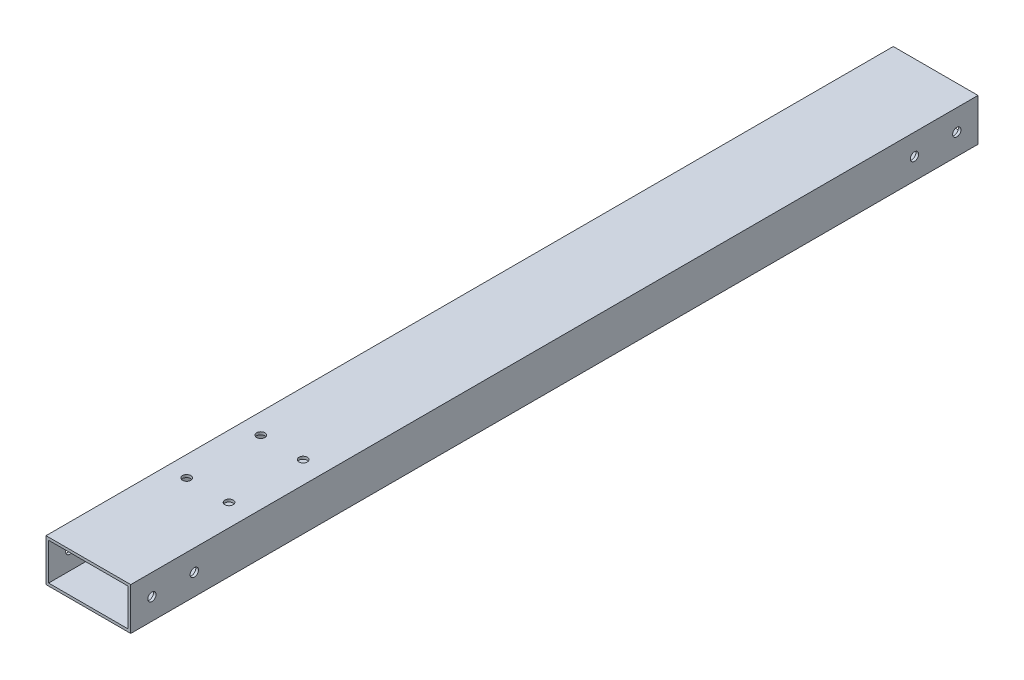
SolidWorks part; units mm, degrees
ref_plane "Front Plane" through (0, 0, 0) normal (0, 0, 1) x (1, 0, 0)
ref_plane "Top Plane" through (0, 0, 0) normal (0, 1, 0) x (1, 0, 0)
ref_plane "Right Plane" through (0, 0, 0) normal (1, 0, 0) x (0, 0, -1)
sketch "Sketch1" plane through (0, 0, 0) normal (0, 0, 1) x (1, 0, 0)
  line L0 (-23.8125, 11.1125) -> (23.8125, 11.1125)
  line L2 (-25.4, 12.7) -> (25.4, 12.7)
  line L3 (-25.4, 12.7) -> (-25.4, -12.7)
  line L4 (-25.4, -12.7) -> (25.4, -12.7)
  line L5 (25.4, 12.7) -> (25.4, -12.7)
  line L10 (23.8125, 11.1125) -> (23.8125, -11.1125)
  line L11 (-23.8125, -11.1125) -> (23.8125, -11.1125)
  line L12 (-23.8125, 11.1125) -> (-23.8125, -11.1125)
  point P12 (0, 12.7)
  point P14 (25.4, 0)
  dimension "Wall Thickness" = 1.5875
  dimension "Outside Width" = 50.8
  dimension "Outside Height" = 25.4
  dimension "Inside Height" = 22.225
  dimension "Inside Width" = 47.625
sketch "Sketch2" plane through (0, 0, 0) normal (1, 0, 0) x (0, 0, -1)
  line L0 (254, 0) -> (-254, 0)
  point P4 (0, 0)
  point P7 (-254, 0)
  point P10 (254, 0)
  dimension "Length" = 508
sketch "Sketch3" plane through (0, 0, 0) normal (0, 0, 1) x (1, 0, 0)
  line L21 (25.4, 12.7) -> (-25.4, 12.7)
  line L22 (25.4, -12.7) -> (25.4, 12.7)
  line L23 (-25.4, -12.7) -> (25.4, -12.7)
  line L24 (-25.4, 12.7) -> (-25.4, -12.7)
  line L25 (25.4, 12.7) -> (-25.4, 12.7)
  line L26 (25.4, -12.7) -> (25.4, 12.7)
  line L27 (-25.4, -12.7) -> (25.4, -12.7)
  line L28 (-25.4, 12.7) -> (-25.4, -12.7)
  line L29 (23.8125, 11.1125) -> (-23.8125, 11.1125)
  line L30 (23.8125, -11.1125) -> (23.8125, 11.1125)
  line L31 (-23.8125, -11.1125) -> (23.8125, -11.1125)
  line L32 (-23.8125, 11.1125) -> (-23.8125, -11.1125)
  line L33 (23.8125, 11.1125) -> (-23.8125, 11.1125)
  line L34 (23.8125, -11.1125) -> (23.8125, 11.1125)
  line L35 (-23.8125, -11.1125) -> (23.8125, -11.1125)
  line L36 (-23.8125, 11.1125) -> (-23.8125, -11.1125)
  dimension "D1" = 0
  dimension "D2" = 0
extrude "Boss-Extrude1" add sketch "Sketch3" along normal up to vertex (254 mm away) and the other way up to vertex (254 mm away) up to point (0, 0, 254) other way up to point (0, 0, -254)
sketch "Drawing Reference" plane through (0, 0, 0) normal (1, 0, 0) x (0, 0, -1)
  line L0 (-254, 0) -> (254, 0) construction
  line L1 (0, -12.7) -> (0, 12.7) construction
  line L2 (-254, -12.7) -> (254, -12.7) construction
  line L5 (-254, 12.7) -> (254, 12.7) construction
  point P7 (-217.424, 0)
  point P8 (217.424, 0)
  dimension "D1" = 36.576
hole_wizard "#10 Clearance Hole1" positions "Sketch4" profile "Sketch5" hole size "#10" standard "ANSI Inch" end condition through all
sketch "Sketch4" plane through (25.4, 0, 0) normal (1, 0, 0) x (0, 0, -1)
  point P0 (-241.3, 0)
  point P3 (-215.9, 0)
  point P6 (215.9, 0)
  point P9 (241.3, 0)
sketch "Sketch5" plane through (25.4, 0, 241.3) normal (0, 1, 0) x (0, 0, -1)
  line L0 (0, 0) -> (0, 50.8)
  line L1 (0, 50.8) -> (2.4892, 50.8)
  line L2 (2.4892, 50.8) -> (2.4892, 0)
  line L5 (2.4892, 0) -> (0, 0)
  line L11 (0, -6.35) -> (0, 107.95) construction
  dimension "Thru Hole Dia." = 4.9784
  dimension "Thru Hole Depth" = 50.8
sketch "Sketch6" plane through (0, 12.7, 0) normal (0, 1, 0) x (1, 0, 0)
  line L0 (-13.208, -137.3969) -> (-13.208, -181.8469) construction
  line L1 (-13.208, -181.8469) -> (12.192, -181.8469) construction
  line L2 (12.192, -181.8469) -> (12.192, -137.3969) construction
  line L3 (12.192, -137.3969) -> (-13.208, -137.3969) construction
  circle A0 centre (-13.208, -181.8469) radius 2.4892 construction
  circle A1 centre (12.192, -181.8469) radius 2.4892 construction
  point P4 (0, 0)
  point P11 (0, 0)
  point P14 (-13.208, -137.3969)
hole_wizard "#10 Clearance Hole2" positions "Sketch9" profile "Sketch10" hole size "#10" standard "ANSI Inch" end condition through all
sketch "Sketch9" plane through (0, 12.7, 0) normal (0, 1, 0) x (1, 0, 0)
  point P0 (12.192, -137.3969)
  point P3 (-13.208, -137.3969)
  point P6 (-13.208, -181.8469)
  point P9 (12.192, -181.8469)
sketch "Sketch10" plane through (12.192, 12.7, 137.3969) normal (1, 0, 0) x (0, 0, 1)
  line L0 (0, 0) -> (0, 25.4)
  line L1 (0, 25.4) -> (2.4892, 25.4)
  line L2 (2.4892, 25.4) -> (2.4892, 0)
  line L5 (2.4892, 0) -> (0, 0)
  line L11 (0, -6.35) -> (0, 107.95) construction
  dimension "Thru Hole Dia." = 4.9784
  dimension "Thru Hole Depth" = 25.4
equation "\"D1@Drawing Reference\"=\"Outside Width@Sketch1\" * 0.72"
